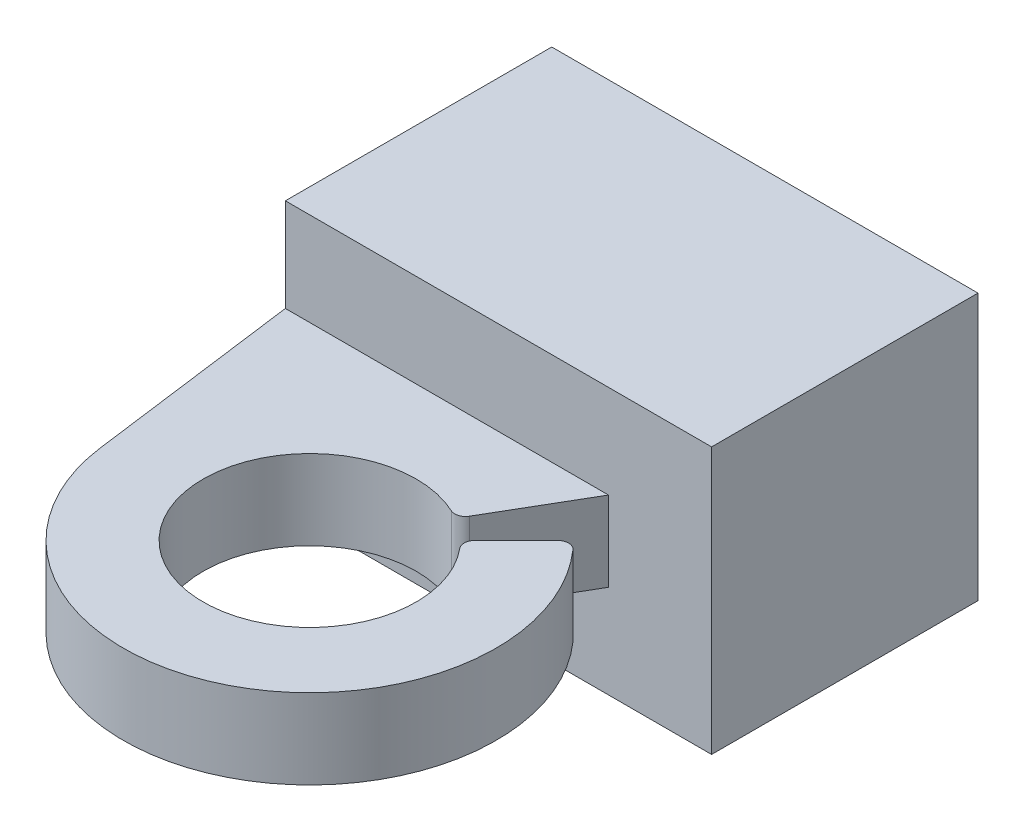
SolidWorks part; units mm, degrees
ref_plane "前视基准面" through (0, 0, 0) normal (0, 0, 1) x (1, 0, 0)
ref_plane "上视基准面" through (0, 0, 0) normal (0, 1, 0) x (1, 0, 0)
ref_plane "右视基准面" through (0, 0, 0) normal (1, 0, 0) x (0, 0, -1)
sketch "草图1" plane through (0, 0, 0) normal (1, 0, 0) x (0, 0, -1)
  line L0 (0, 0) -> (11989.1422, 0) construction
  line L1 (0, 0) -> (0, 11989.1422) construction
  line L3 (-2.5, -2.5) -> (2.5, -2.5)
  line L4 (-2.5, -2.5) -> (-2.5, 2.5)
  line L5 (-2.5, 2.5) -> (2.5, 2.5)
  line L6 (2.5, -2.5) -> (2.5, 2.5)
  line L7 (-2.5, -2.5) -> (2.5, 2.5) construction
  line L8 (-2.5, 2.5) -> (2.5, -2.5) construction
  point P5 (0, 0)
  dimension "D1" = 5
  dimension "D2" = 5
extrude "凸台-拉伸1" add sketch "草图1" along normal blind 8
sketch "草图2" plane through (0, 0, 0) normal (-1, 0, 0) x (0, 0, 1)
  circle A0 centre (0, 0) radius 2
  dimension "D1" = 4
extrude "切除-拉伸1" cut sketch "草图2" against normal blind 7
sketch "草图3" plane through (0, 2.5, 0) normal (0, 1, 0) x (1, 0, 0)
  line L0 (0, 0) -> (8, 0) construction
  line L1 (8, 2.5) -> (8, -2.5) construction
  line L3 (1.5, 0.2) -> (6.5, 0.2)
  line L4 (1.5, 0.2) -> (1.5, -0.2)
  line L5 (1.5, -0.2) -> (6.5, -0.2)
  line L6 (6.5, 0.2) -> (6.5, -0.2)
  line L7 (1.5, 0.2) -> (6.5, -0.2) construction
  line L8 (1.5, -0.2) -> (6.5, 0.2) construction
  point P5 (4, 0)
  dimension "D1" = 5
  dimension "D2" = 0.4
extrude "凸台-拉伸2" add sketch "草图3" against normal blind 0.6
fillet "圆角1" radius 0.2 3 edges at (4, 1.9, 0.2) (4, 1.9, -0.2) (1.5, 1.9, 0)
pattern_circular "阵列(圆周)1" count 3 every 120 about axis through (7, 0, 0) along (-1, 0, 0) of "圆角1", "凸台-拉伸2" reverse direction yes
sketch "草图4" plane through (0, 0, 0) normal (0, 1, 0) x (1, 0, 0)
  line L0 (4, -2.5) -> (4, -6.0432) construction
  line L1 (8, -2.5) -> (0, -2.5) construction
  line L2 (0, -2.5) -> (0.5303, -6.5029)
  line L3 (5.007, -4.3152) -> (6.0647, -2.5)
  line L4 (5.4142, -4.629) -> (6.4749, -3.5683)
  line L5 (4, -6.0432) -> (15.0688, -6.0432) construction
  line L6 (0, -2.5) -> (6.0647, -2.5)
  arc A0 (0.5303, -6.5029) -> (6.4749, -3.5683) centre (4, -6.0432) ccw
  arc A1 (5.007, -4.3152) -> (5.4142, -4.629) centre (4, -6.0432) ccw
  dimension "D1" = 7
  dimension "D2" = 4
  dimension "D3" = 45
extrude "凸台-拉伸3" add sketch "草图4" along normal mid plane 1.5
fillet "圆角2" radius 0.2 2 edges at (6.4749, 0, 3.5683) (5.4142, 0, 4.629)
fillet "圆角3" radius 0.2 1 edges at (5.007, 0, 4.3152)
